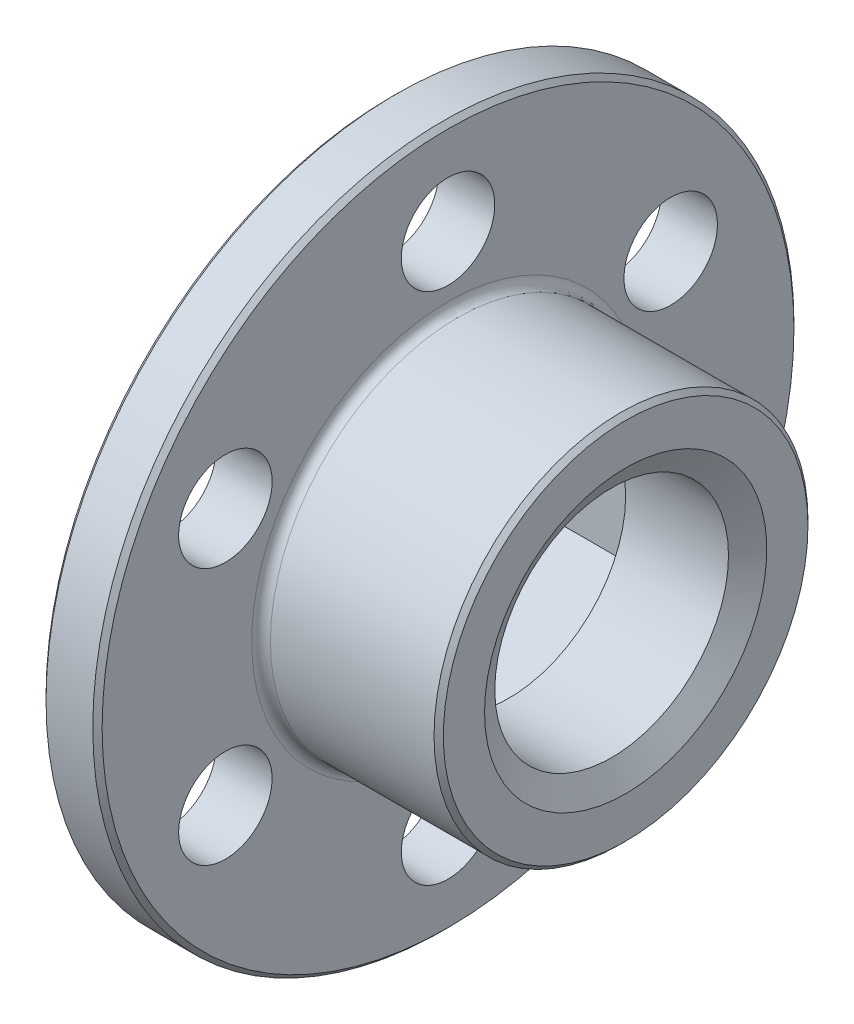
SolidWorks part; units mm, degrees
ref_plane "Спереди" through (0, 0, 0) normal (0, 0, 1) x (1, 0, 0)
ref_plane "Сверху" through (0, 0, 0) normal (0, 1, 0) x (1, 0, 0)
ref_plane "Справа" through (0, 0, 0) normal (1, 0, 0) x (0, 0, -1)
sketch "Эскиз1" plane through (0, 0, 0) normal (0, 0, 1) x (1, 0, 0)
  line L0 (0, 0) -> (0, 75)
  line L1 (0, 75) -> (12, 75)
  line L2 (12, 75) -> (12, 40)
  line L3 (12, 40) -> (50, 40)
  line L4 (50, 40) -> (50, 0)
  line L5 (0, 0) -> (90.8608, 0) construction
  line L6 (-8.2658, 55) -> (23.2876, 55) construction
  line L7 (0, 65) -> (12, 65)
  line L8 (0, 55) -> (12, 55)
  line L9 (0, 25) -> (50, 25)
  dimension "D1" = 150
  dimension "D2" = 80
  dimension "D3" = 50
  dimension "D4" = 38
  dimension "D5" = 55
  dimension "D6" = 20
  dimension "D7" = 50
revolve "Повернуть1" add sketch "Эскиз1" angle 360 about L5 region at (21.3226, 35.4032, 0) region at (6, 60, 0) region at (6, 70, 0)
fillet "Скругление2" radius 2 1 edges at (12, 0, 40)
chamfer "Фаска2" distance 1 angle 45 3 edges at (50, 0, 40) (0, 0, 75) (12, 0, 75)
revolve "Вырез-Повернуть1" cut sketch "Эскиз1<8>" angle 360 about L6 region at (6, 60, 0)
sketch "Эскиз1<8>" plane through (0, 0, 0) normal (0, 0, 1) x (1, 0, 0) same geometry as "Эскиз1"
ref_axis "Ось1" through (50, 0, 0) along (-1, 0, 0)
pattern_circular "Круговой массив1" count 6 over 360 about axis through (50, 0, 0) along (-1, 0, 0) of "Вырез-Повернуть1"
sketch "Эскиз2" plane through (0, 0, 0) normal (0, 1, 0) x (1, 0, 0)
  line L0 (0, 0) -> (80.3219, 0) construction
  line L1 (50, 25) -> (47, 25)
  line L3 (32.5662, 0) -> (50, 30.1962)
  line L4 (50, 30.1962) -> (50, 25)
  line L5 (50, 25) -> (0, 25) construction
  line L7 (50, -39) -> (50, 39) construction
  dimension "D1" = 60
  dimension "D2" = 3
revolve "Вырез-Повернуть3" cut sketch "Эскиз2" angle 360 about L0 region at (49, 0, -26.7321)
ref_plane "Плоскость1" through (25, 0, 0) normal (1, 0, 0) x (0, 0, -1)
sketch "Эскиз3" plane through (25, 0, 0) normal (1, 0, 0) x (0, 0, -1)
  line L1 (0, 35) -> (-30.3109, 17.5)
  line L2 (-30.3109, 17.5) -> (-30.3109, -17.5)
  line L3 (-30.3109, -17.5) -> (0, -35)
  line L4 (0, -35) -> (30.3109, -17.5)
  line L5 (30.3109, -17.5) -> (30.3109, 17.5)
  line L6 (30.3109, 17.5) -> (0, 35)
  circle A0 centre (0, 0) radius 30.3109 construction
  dimension "D1" = 70
extrude "Вырез-Вытянуть1" cut sketch "Эскиз3" against normal through all
